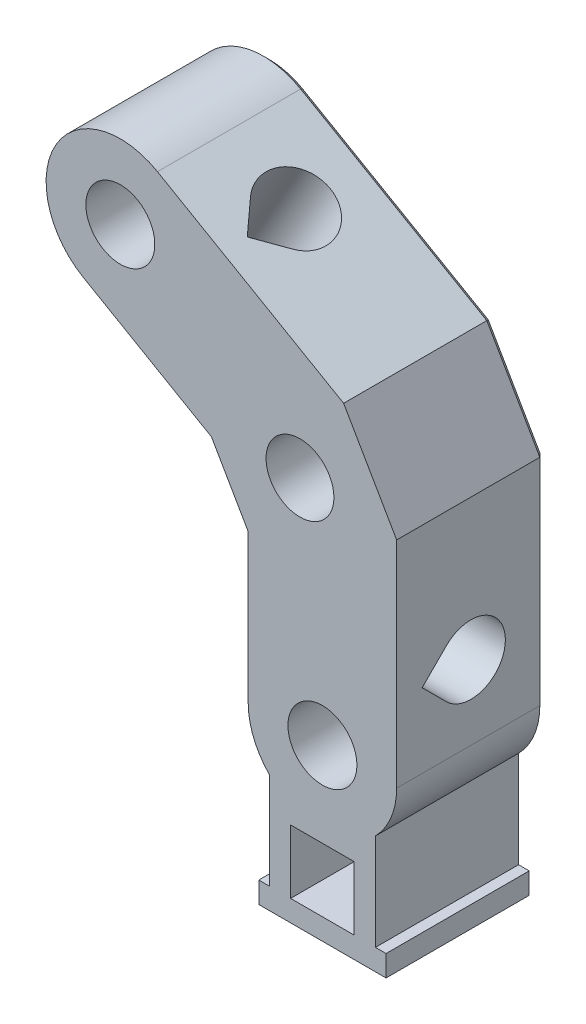
SolidWorks part; units mm, degrees
material "ABS"
ref_plane "Front Plane" through (0, 0, 0) normal (0, 0, 1) x (1, 0, 0)
ref_plane "Top Plane" through (0, 0, 0) normal (0, 1, 0) x (1, 0, 0)
ref_plane "Right Plane" through (0, 0, 0) normal (1, 0, 0) x (0, 0, -1)
ref_plane "Plane4" through (0, 0, 14) normal (0, 0, 1) x (1, 0, 0)
sketch "Sketch1" plane through (0, 0, 14) normal (0, 0, 1) x (1, 0, 0)
  line L0 (7, 0) -> (7, 20.2679)
  line L1 (7, 20.2679) -> (2, 28.9282)
  line L2 (2, 28.9282) -> (-15.5526, 39.0622)
  line L3 (-22.5526, 26.9378) -> (-10.4641, 19.9585)
  line L4 (-10.4641, 19.9585) -> (-7, 13.9585)
  line L5 (-7, 13.9585) -> (-7, 0)
  line L6 (-8.7321, 16.9585) -> (4.5, 24.5981) construction
  line L7 (0, 0) -> (0, -16) construction
  line L8 (-6, -14) -> (-5, -14)
  line L9 (-6, -14) -> (-6, -16)
  line L10 (-6, -16) -> (6, -16)
  line L11 (6, -14) -> (6, -16)
  line L13 (-5, -14) -> (-5, -4.899)
  line L14 (5, -14) -> (6, -14)
  line L15 (5, -14) -> (5, -4.899)
  line L16 (-3, -14) -> (3, -14)
  line L17 (-3, -14) -> (-3, -8)
  line L18 (-3, -8) -> (3, -8)
  line L19 (3, -14) -> (3, -8)
  arc A0 (-15.5526, 39.0622) -> (-22.5526, 26.9378) centre (-19.0526, 33) ccw
  arc A1 (-7, 0) -> (-5, -4.899) centre (0, 0) ccw
  arc A2 (5, -4.899) -> (7, 0) centre (0, 0) ccw
  dimension "D2" = 7
  dimension "D1" = 120
  dimension "D3" = 150
  dimension "D4" = 10
  dimension "D5" = 38.1051
  dimension "D6" = 12
  dimension "D7" = 10
  dimension "D8" = 6
  dimension "D9" = 6
  dimension "D10" = 3
  dimension "D11" = 16
  dimension "D12" = 2
  dimension "D13" = 5
extrude "Boss-Extrude1" add sketch "Sketch1" against normal blind 14
hole_wizard "Hole2" positions "Sketch7" profile "Sketch6" legacy end condition through all
sketch "Sketch7" plane through (0, 0, 0) normal (0, 0, -1) x (-1, 0, 0)
  line L0 (0, 0) -> (19.0525, 32.9999) construction
  line L2 (0, 0) -> (22.3725, 0) construction
  point P0 (19.0525, 32.9999)
  dimension "D1" = 38.105
  dimension "D2" = 60
sketch "Sketch6" plane through (-19.0525, 32.9999, 0) normal (1, 0, 0) x (0, 1, 0)
  line L0 (0, 0) -> (0, 14)
  line L1 (0, 14) -> (3.25, 14)
  line L2 (3.25, 14) -> (3.25, 0)
  line L3 (3.25, 0) -> (0, 0)
  line L4 (0, 110) -> (0, -10) construction
  dimension "Diameter" = 6.5
  dimension "Depth" = 14
hole_wizard "Hole1" positions "Sketch5" profile "Sketch4" legacy end condition through all
sketch "Sketch5" plane through (0, 0, 0) normal (0, 0, -1) x (-1, 0, 0)
  point P0 (0, 0)
sketch "Sketch4" plane through (0, 0, 0) normal (1, 0, 0) x (0, 1, 0)
  line L0 (0, 0) -> (0, 14)
  line L1 (0, 14) -> (3.25, 14)
  line L2 (3.25, 14) -> (3.25, 0)
  line L3 (3.25, 0) -> (0, 0)
  line L4 (0, 110) -> (0, -10) construction
  dimension "Diameter" = 6.5
  dimension "Depth" = 14
ref_axis "Axis1" through (-19.0525, 32.9999, 14) along (0, 0, -1)
sketch "Sketch3" plane through (-7, 0, 0) normal (-1, 0, 0) x (0, 0, 1)
  line L0 (9.2981, 4.7019) -> (11.5962, 7)
  line L1 (11.5962, 7) -> (9.2981, 9.2981)
  line L2 (0, 13.9585) -> (0, 0) construction
  line L3 (7, 7) -> (7, 0) construction
  line L4 (0, 0) -> (14, 0) construction
  arc A0 (9.2981, 9.2981) -> (9.2981, 4.7019) centre (7, 7) ccw
  dimension "D1" = 3.25
  dimension "D2" = 45
  dimension "D3" = 7
extrude "Cut-Extrude2" cut sketch "Sketch3" against normal through all
sketch "Sketch2" plane through (6.0263, 10.4378, 0) normal (-0.5, -0.866, 0) x (0.866, -0.5, 0)
  line L0 (-25.9999, 11.5962) -> (-28.298, 9.2981)
  line L1 (-23.7018, 9.2981) -> (-25.9999, 11.5962)
  line L2 (-25.9999, 7) -> (-33, 7) construction
  line L3 (-33, 0) -> (-33, 14) construction
  line L4 (-32.9999, 14) -> (-32.9999, 0) construction
  arc A0 (-28.298, 9.2981) -> (-23.7018, 9.2981) centre (-25.9999, 7) ccw
  dimension "D1" = 7
  dimension "D3" = 3.25
  dimension "D2" = 45
extrude "Cut-Extrude1" cut sketch "Sketch2" against normal through all
sketch "Sketch8" plane through (0, 0, 14) normal (0, 0, 1) x (1, 0, 0)
  line L0 (-8.7321, 16.9585) -> (4.5, 24.5981) construction
  line L1 (-10.4641, 19.9585) -> (-7, 13.9585) construction
  line L2 (7, 20.2679) -> (2, 28.9282) construction
  circle A0 centre (-2.116, 20.7783) radius 3.2
  dimension "D1" = 6.4
extrude "Cut-Extrude3" cut sketch "Sketch8" against normal through all
chamfer "Chamfer1" distance 0.5 angle 45 23 edges at (-22.3025, 32.9999, 0) (-3.25, 0, 0) (1.084, 20.7783, 0) (0, -16, 0) (6, -15, 0) (5.5, -14, 0) (5, -9.4495, 0) (6.4807, -2.6458, 0) (7, 10.134, 0) (4.5, 24.5981, 0) (-6.7763, 33.9952, 0) (-25.1147, 36.5, 0) (-16.5083, 23.4482, 0) (-8.7321, 16.9585, 0) (-7, 6.9793, 0) (-6.4807, -2.6458, 0) (-5, -9.4495, 0) (-5.5, -14, 0) (-6, -15, 0) (0, -8, 0) (3, -11, 0) (0, -14, 0) (-3, -11, 0)
equation "\"Diameter@Sketch4\" = 6.5"
equation "\"Diameter@Sketch6\"= 6.5"
